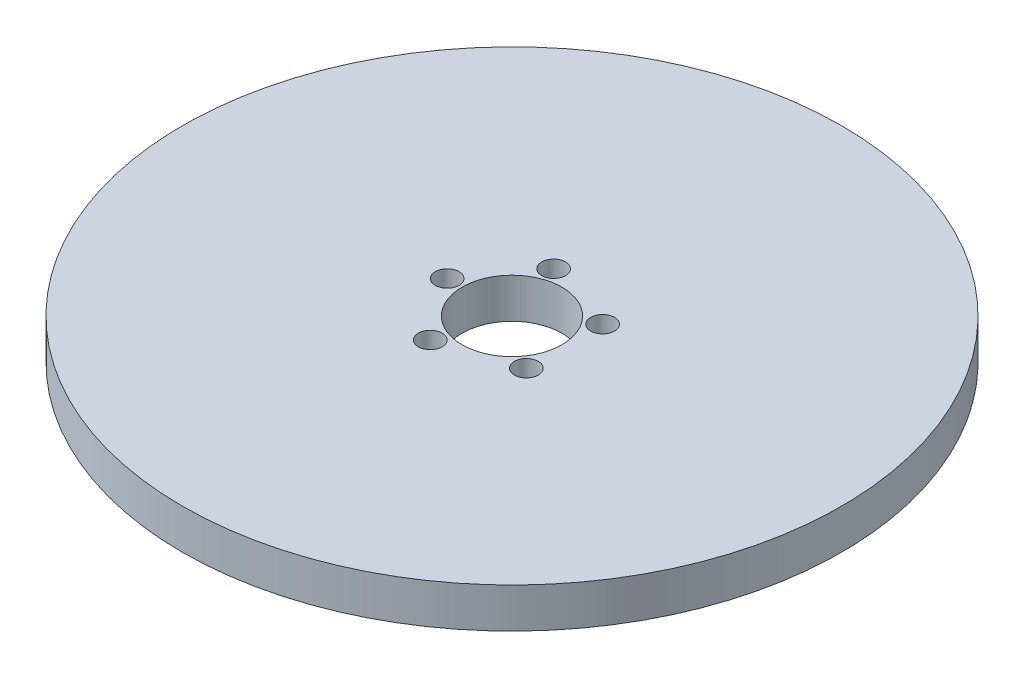
SolidWorks part; units mm, degrees
ref_plane "Front Plane" through (0, 0, 0) normal (0, 0, 1) x (1, 0, 0)
ref_plane "Top Plane" through (0, 0, 0) normal (0, 1, 0) x (1, 0, 0)
ref_plane "Right Plane" through (0, 0, 0) normal (1, 0, 0) x (0, 0, -1)
sketch "Sketch1" plane through (0, 0, 0) normal (0, 1, 0) x (1, 0, 0)
  circle A0 centre (0, 0) radius 82.5
  dimension "FLANGE_OD" = 165
extrude "Boss-Extrude1" add sketch "Sketch1" along normal blind 10
sketch "Sketch2" plane through (0, 0, 0) normal (0, 1, 0) x (1, 0, 0)
  circle A0 centre (0, 0) radius 12.5
  dimension "BORE_D" = 25
extrude "Cut-Extrude1" cut sketch "Sketch2" along normal through all
sketch "Sketch3" plane through (0, 10, 0) normal (0, 1, 0) x (1, 0, 0)
  circle A0 centre (0, 0) radius 16.2331 construction
  circle A1 centre (-16.2331, 0) radius 2.9814
  dimension "BOLT_D" = 5.9628
  dimension "BOLT_PCD" = 32.4662
extrude "Cut-Extrude2" cut sketch "Sketch3" against normal blind 9.0502
pattern_circular "CirPattern1" count 5 over 360 about axis through (0, 0, 0) along (0, 1, 0) of "Cut-Extrude2"
